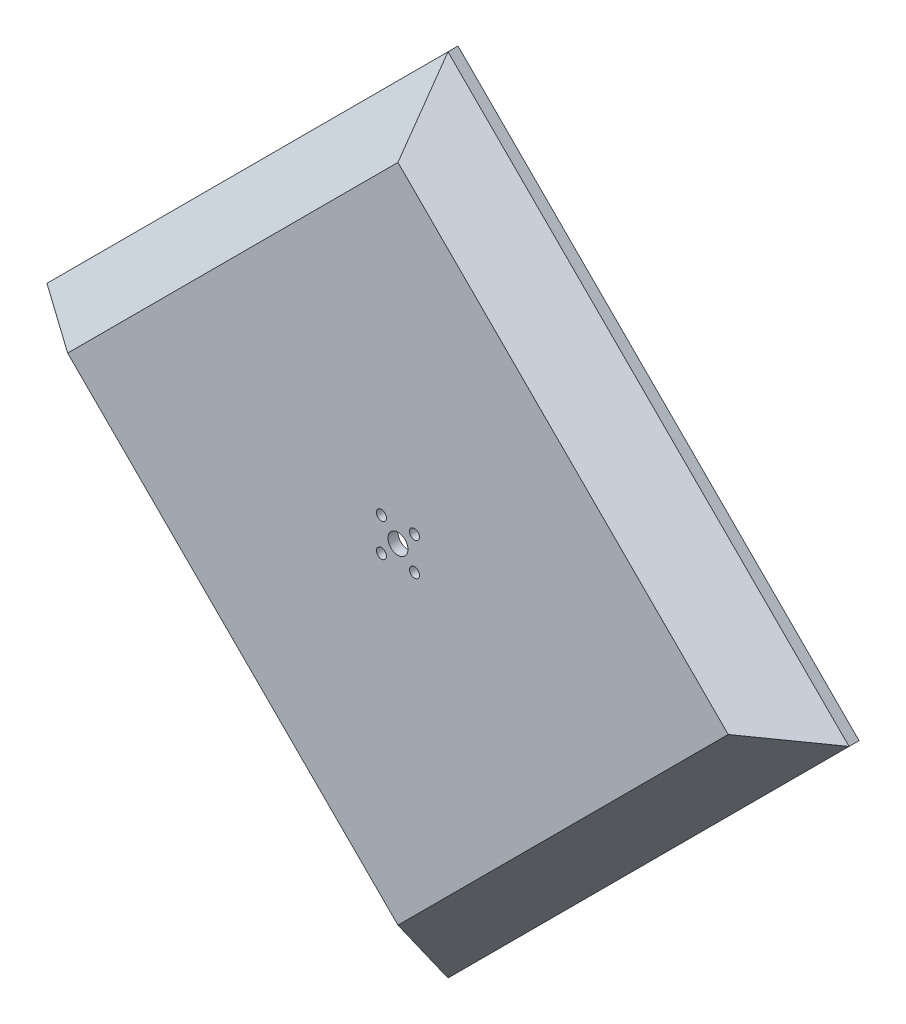
SolidWorks part; units mm, degrees
ref_plane "前视基准面" through (0, 0, 0) normal (0, 0, 1) x (1, 0, 0)
ref_plane "上视基准面" through (0, 0, 0) normal (0, 1, 0) x (1, 0, 0)
ref_plane "右视基准面" through (0, 0, 0) normal (1, 0, 0) x (0, 0, -1)
sketch "草图1" plane through (0, 0, 0) normal (0, 0, 1) x (1, 0, 0)
  line L1 (85, -85) -> (-85, -85)
  line L2 (85, -85) -> (85, 85)
  line L3 (85, 85) -> (-85, 85)
  line L4 (-85, -85) -> (-85, 85)
  line L5 (85, -85) -> (-85, 85) construction
  line L6 (85, 85) -> (-85, -85) construction
  point P0 (0, 0)
  dimension "D1" = 170
  dimension "D2" = 170
extrude "凸台-拉伸1" add sketch "草图1" along normal blind 3
sketch "草图3" plane through (0, 0, 0) normal (0, 0, -1) x (-1, 0, 0)
  line L1 (4.95, -4.95) -> (-4.95, -4.95) construction
  line L2 (4.95, -4.95) -> (4.95, 4.95) construction
  line L3 (4.95, 4.95) -> (-4.95, 4.95) construction
  line L4 (-4.95, -4.95) -> (-4.95, 4.95) construction
  line L5 (4.95, -4.95) -> (-4.95, 4.95) construction
  line L6 (4.95, 4.95) -> (-4.95, -4.95) construction
  circle A0 centre (0, 0) radius 3
  circle A1 centre (4.95, 4.95) radius 1.5
  circle A2 centre (-4.95, 4.95) radius 1.5
  circle A3 centre (-4.95, -4.95) radius 1.5
  circle A4 centre (4.95, -4.95) radius 1.5
  point P0 (0, 0)
  dimension "D1" = 6
  dimension "D2" = 3
  dimension "D3" = 3
  dimension "D4" = 3
  dimension "D5" = 3
  dimension "D6" = 9.9
  dimension "D7" = 9.9
extrude "切除-拉伸1" cut sketch "草图3" against normal through all
fillet "圆角1" radius 2 4 edges at (85, -85, 1.5) (85, 85, 1.5) (-85, -85, 1.5) (-85, 85, 1.5)
sketch "草图4" plane through (0, 0, 0) normal (0, 0, -1) x (-1, 0, 0)
  line L0 (0, 0) -> (22.2376, 22.2376) construction
  line L1 (60.1041, -60.1041) -> (-60.1041, 60.1041)
  line L2 (35.2082, -85) -> (85, -35.2082)
  line L3 (-85, 35.2082) -> (-35.2082, 85)
  line L4 (-85, 83) -> (-85, -83)
  line L5 (-83, -85) -> (83, -85)
  line L6 (85, -83) -> (85, 83)
  line L7 (83, 85) -> (-83, 85)
  line L8 (-85, 83) -> (-85, -83)
  line L9 (-83, -85) -> (83, -85)
  line L10 (85, -83) -> (85, 83)
  line L11 (83, 85) -> (-83, 85)
  line L12 (-60.1041, -60.1041) -> (60.1041, 60.1041)
  line L13 (-60.1041, -60.1041) -> (-85, -36.1123)
  line L14 (-60.1041, -60.1041) -> (-34.2699, -85)
  line L15 (60.1041, 60.1041) -> (85, 34.2699)
  line L16 (60.1041, 60.1041) -> (36.1123, 85)
  arc A4 (-85, -83) -> (-83, -85) centre (-83, -83) ccw
  arc A5 (83, -85) -> (85, -83) centre (83, -83) ccw
  arc A6 (85, 83) -> (83, 85) centre (83, 83) ccw
  arc A7 (-83, 85) -> (-85, 83) centre (-83, 83) ccw
  arc A8 (-85, -83) -> (-83, -85) centre (-83, -83) ccw
  arc A9 (83, -85) -> (85, -83) centre (83, -83) ccw
  arc A10 (85, 83) -> (83, 85) centre (83, 83) ccw
  arc A11 (-83, 85) -> (-85, 83) centre (-83, 83) ccw
  line M18 (-85, 83) -> (-85, -83)
  line M20 (-83, -85) -> (83, -85)
  arc M21 (83, -85) -> (85, -83) centre (83, -83) ccw
  line M22 (85, -83) -> (85, 83)
  line M24 (83, 85) -> (-83, 85)
  arc M25 (-83, 85) -> (-85, 83) centre (-83, 83) ccw
  dimension "D2" = 85
  dimension "D3" = 85
  dimension "D1" = 0
extrude "切除-拉伸2" cut sketch "草图4" against normal blind 10 contours L3 M18 M24 M25 | L2 M20 M21 M22 region at (-68.3915, -68.3915, 0) region at (68.3915, 68.3915, 0)
sketch "草图5" plane through (0, 0, 0) normal (0, 0, -1) x (-1, 0, 0)
  line L0 (-35.2082, 85) -> (24.3101, 144.5183)
  line L1 (24.3101, 144.5183) -> (144.5183, 24.3101)
  line L2 (0, 0) -> (-60.1041, 60.1041) construction
  line L3 (-85, 35.2082) -> (-35.2082, 85) construction
  line L4 (0, 0) -> (84.4142, 84.4142) construction
  line L5 (-85, -83) -> (-85, 35.2082)
  line L6 (-144.5183, -24.3101) -> (-24.3101, -144.5183)
  line L7 (-85, 35.2082) -> (-144.5183, -24.3101)
  line L8 (85, -35.2082) -> (144.5183, 24.3101)
  line L9 (35.2082, -85) -> (-24.3101, -144.5183)
  line L11 (83, 85) -> (-35.2082, 85)
  line L12 (-35.2082, 85) -> (-85, 35.2082)
  line L13 (-85, 35.2082) -> (-85, -83)
  line L14 (-83, -85) -> (35.2082, -85)
  line L15 (35.2082, -85) -> (85, -35.2082)
  line L16 (85, -35.2082) -> (85, 83)
  line L17 (83, 85) -> (-35.2082, 85)
  line L18 (-35.2082, 85) -> (-85, 35.2082)
  line L19 (-85, 35.2082) -> (-85, -83)
  line L20 (-83, -85) -> (35.2082, -85)
  line L21 (35.2082, -85) -> (85, -35.2082)
  line L22 (85, -35.2082) -> (85, 83)
  arc A0 (85, 83) -> (83, 85) centre (83, 83) ccw construction
  arc A3 (-85, -83) -> (-83, -85) centre (-83, -83) ccw
  arc A4 (85, 83) -> (83, 85) centre (83, 83) ccw
  arc A5 (-85, -83) -> (-83, -85) centre (-83, -83) ccw
  arc A6 (85, 83) -> (83, 85) centre (83, 83) ccw
  point P25 (-84.4142, -84.4142)
  dimension "D1" = 0
sketch "草图6" plane through (0, 0, 0) normal (0, 0, -1) x (-1, 0, 0)
  line L0 (-60.1041, -60.1041) -> (60.1041, 60.1041)
  line L1 (0, 0) -> (84.4142, 84.4142) construction
  line L2 (0, 0) -> (-32.158, 32.158)
  line L3 (0, 0) -> (-60.1041, 60.1041) construction
  line L4 (60.1041, 60.1041) -> (35.2082, 85)
  line L5 (60.1041, 60.1041) -> (85, 35.2082)
  line L6 (83, 85) -> (-35.2082, 85)
  line L7 (-35.2082, 85) -> (-85, 35.2082)
  line L8 (-85, 35.2082) -> (-85, -83)
  line L9 (-83, -85) -> (35.2082, -85)
  line L10 (35.2082, -85) -> (85, -35.2082)
  line L11 (85, -35.2082) -> (85, 83)
  line L12 (83, 85) -> (-35.2082, 85)
  line L13 (-35.2082, 85) -> (-85, 35.2082)
  line L14 (-85, 35.2082) -> (-85, -83)
  line L15 (-83, -85) -> (35.2082, -85)
  line L16 (35.2082, -85) -> (85, -35.2082)
  line L17 (85, -35.2082) -> (85, 83)
  line L18 (-60.1041, -60.1041) -> (-35.2082, -85)
  line L19 (-60.1041, -60.1041) -> (-85, -35.2082)
  arc A2 (-85, -83) -> (-83, -85) centre (-83, -83) ccw
  arc A3 (85, 83) -> (83, 85) centre (83, 83) ccw
  arc A4 (-85, -83) -> (-83, -85) centre (-83, -83) ccw
  arc A5 (85, 83) -> (83, 85) centre (83, 83) ccw
  line M18 (83, 85) -> (-35.2082, 85)
  arc M21 (-85, -83) -> (-83, -85) centre (-83, -83) ccw
  line M22 (-83, -85) -> (35.2082, -85)
  line M24 (85, -35.2082) -> (85, 83)
  arc M25 (85, 83) -> (83, 85) centre (83, 83) ccw
  dimension "D2" = 85
  dimension "D1" = 0
extrude "切除-拉伸3" cut sketch "草图6" against normal blind 3 contours L18 L19 L14 M21 M22 | L4 L5 M24 M25 M18 region at (68.3915, -68.3915, 0) region at (-68.3915, 68.3915, 0)
sketch "草图7" plane through (0, 0, 0) normal (0, 0, -1) x (-1, 0, 0)
  line L0 (-120.2082, 0) -> (0, 120.2082)
  line L1 (-35.2082, 85) -> (24.3101, 144.5183) construction
  line L2 (0, 120.2082) -> (35.2082, 85)
  line L3 (0, 0) -> (-21.4242, 21.4242)
  line L4 (0, 0) -> (-60.1041, 60.1041) construction
  line L5 (0, 0) -> (24.2164, 24.2164)
  line L6 (0, 0) -> (84.4142, 84.4142) construction
  line L7 (-120.2082, 0) -> (-85, -35.2082)
  line L8 (-85, -35.2082) -> (-35.2082, -85)
  line L9 (-35.2082, -85) -> (35.2082, -85)
  line L10 (35.2082, -85) -> (85, -35.2082)
  line L11 (85, -35.2082) -> (85, 35.2082)
  line L12 (85, 35.2082) -> (35.2082, 85)
  line L13 (35.2082, 85) -> (-35.2082, 85)
  line L14 (-35.2082, 85) -> (-85, 35.2082)
  line L15 (-85, 35.2082) -> (-85, -35.2082)
  line L16 (-85, -35.2082) -> (-35.2082, -85)
  line L17 (-35.2082, -85) -> (35.2082, -85)
  line L18 (35.2082, -85) -> (85, -35.2082)
  line L19 (85, -35.2082) -> (85, 35.2082)
  line L20 (85, 35.2082) -> (35.2082, 85)
  line L21 (35.2082, 85) -> (-35.2082, 85)
  line L22 (-35.2082, 85) -> (-85, 35.2082)
  line L23 (-85, 35.2082) -> (-85, -35.2082)
  line L24 (85, 35.2082) -> (85, -35.2082)
  line L25 (120.2082, 0) -> (85, 35.2082)
  line L26 (35.2082, -85) -> (-35.2082, -85)
  line L27 (0, -120.2082) -> (-35.2082, -85)
  line L28 (0, -120.2082) -> (120.2082, 0)
  point P22 (-60.1041, 60.1041)
  line M19 (-35.2082, -85) -> (35.2082, -85)
  line M21 (85, -35.2082) -> (85, 35.2082)
  line M23 (35.2082, 85) -> (-35.2082, 85)
  line M25 (-85, 35.2082) -> (-85, -35.2082)
  dimension "D1" = 0
extrude "凸台-拉伸4" add sketch "草图7" against normal blind 3 contours L0 L7 M25 | L2 L0 M23 | L27 L28 M19 | L28 L25 M21 region at (96.7361, 0, 0) region at (0, 96.7361, 0) region at (0, -96.7361, 0) region at (-96.7361, 0, 0)
sketch "草图8" plane through (-60.1041, 60.1041, 0) normal (-0.7071, 0.7071, 0) x (0, 0, 1)
  line L0 (0, 85) -> (-15, 85)
  line L1 (-15, 85) -> (0, 70)
  line L2 (0, -85) -> (0, 85) construction
  line L3 (0, 70) -> (0, 73)
  line L4 (0, 73) -> (-12, 85)
  line M3 (0, 85) -> (0, -85)
  dimension "D1" = 15
  dimension "D2" = 15
  dimension "D3" = 3
  dimension "D4" = 3
extrude "凸台-拉伸5" add sketch "草图8" against normal up to vertex (170 mm away) contours L4 L0 L1 M3 region at (-4.7926, 115.4155, -6.7778) up to point (120.2082, 0, 3)
pattern_circular "阵列(圆周)1" count 4 over 360 about axis through (0, 0, 0) along (0, 0, -1) of "凸台-拉伸5"
sketch "草图9" plane through (60.1041, 60.1041, 0) normal (0.7071, 0.7071, 0) x (0, 0, -1)
  line L0 (-3, 85) -> (12, 85)
  line L1 (12, 85) -> (-3, 70)
  line L2 (-3, 85) -> (-3, -85) construction
  line L3 (-3, 70) -> (-3, 85)
extrude "切除-拉伸4" cut sketch "草图9" against normal blind 179
pattern_circular "阵列(圆周)2" count 4 over 360 about axis through (0, 0, 0) along (0, 0, -1) of "切除-拉伸4"
